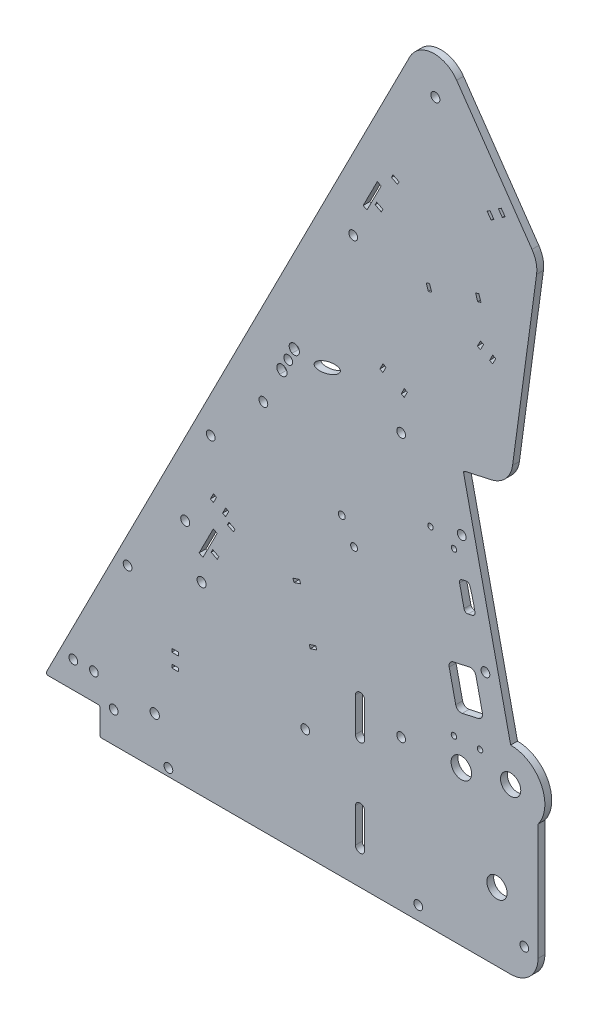
SolidWorks part; units mm, degrees
other "Markup1"
sketch "Sketch5"
ref_plane "Front Plane" through (0, 0, 0) normal (0, 0, 1) x (1, 0, 0)
ref_plane "Top Plane" through (0, 0, 0) normal (0, 1, 0) x (1, 0, 0)
ref_plane "Right Plane" through (0, 0, 0) normal (1, 0, 0) x (0, 0, -1)
sketch "Sketch1" plane through (0, 0, 0) normal (0, 0, 1) x (1, 0, 0)
  line L1 (228.6, -12.7) -> (228.6, 53.975)
  line L2 (178.7547, 351.4131) -> (0, 0)
  line L3 (228.6, 279.4) -> (178.7547, 351.4131)
  line L5 (0, 0) -> (25.4, 0)
  line L6 (25.4, 0) -> (25.4, -12.7)
  line L7 (25.4, -12.7) -> (228.6, -12.7)
  line L9 (215.9, 79.375) -> (193.9097, 178.5667)
  line L10 (193.9097, 178.5667) -> (215.6079, 183.377)
  line L11 (215.6079, 183.377) -> (228.6, 279.4)
  arc A0 (228.6, 53.975) -> (215.9, 79.375) centre (215.9, 63.5) ccw
  dimension "D7" = 12.7
  dimension "D8" = 76.2
  dimension "D10" = 31.75
  dimension "D2" = 292.1
  dimension "D3" = 25.4
  dimension "D4" = 215.9
  dimension "D5" = 394.2644
  dimension "D6" = 203.2
  dimension "D9" = 63.039
  dimension "D11" = 101.6
  dimension "D12" = 12.5
  dimension "D13" = 22.225
extrude "Boss-Extrude1" add sketch "Sketch1" along normal blind 3.175
sketch "Sketch2" plane through (0, 0, 3.175) normal (0, 0, 1) x (1, 0, 0)
  line L0 (178.7547, 351.4131) -> (0, 0) construction
  line L1 (25.4, -12.7) -> (228.6, -12.7) construction
  line L2 (215.9, 79.375) -> (193.9097, 178.5667) construction
  line L3 (193.9097, 178.5667) -> (215.6079, 183.377) construction
  line L4 (215.9, 79.375) -> (193.9097, 178.5667) construction
  line L5 (64.9432, 94.0578) -> (72.5445, 73.1732) construction
  line L6 (64.9432, 94.0578) -> (89.8317, 94.0578) construction
  line L10 (228.6, -12.7) -> (228.6, 53.975) construction
  circle A0 centre (64.9432, 94.0578) radius 2.0955
  circle A1 centre (180.975, 322.1643) radius 2.0955
  circle A2 centre (72.5445, 73.1732) radius 2.0955
  circle A3 centre (193.2078, 152.3944) radius 2.032
  circle A4 centre (215.9, 63.5) radius 4.699
  circle A7 centre (173.0375, -6.35) radius 2.032
  circle A8 centre (204.203, 102.7985) radius 2.032
  circle A26 centre (209.55, 19.05) radius 4.699
  arc A30 (228.6, 53.975) -> (215.9, 79.375) centre (215.9, 63.5) ccw construction
  circle A31 centre (165.1, 179.3875) radius 2.032
  point P5 (77.3874, 112.6024)
  point P17 (78.6277, 76.5455)
  dimension "D3" = 4.191
  dimension "D5" = 4.191
  dimension "D9" = 4.191
  dimension "D20" = 9.398
  dimension "D23" = 9.398
  dimension "D18" = 4.064
  dimension "D26" = 4.064
  dimension "D14" = 4.064
  dimension "D2" = 15.24
  dimension "D6" = 15.24
  dimension "D7" = 22.225
  dimension "D21" = 44.45
  dimension "D22" = 6.35
  dimension "D19" = 160.3375
  dimension "D24" = 44.45
  dimension "D25" = 6.35
  dimension "D27" = 25.4
  dimension "D28" = 50.8
  dimension "D29" = 6.35
  dimension "D17" = 6.35
  dimension "D33" = 55.5625
  dimension "D15" = 114.3
  dimension "D4" = 180.975
  dimension "D8" = 70
extrude "Cut-Extrude1" cut sketch "Sketch2" against normal through all
sketch "Sketch7" plane through (0, 0, 3.175) normal (0, 0, 1) x (1, 0, 0)
  line L0 (146.05, 3.175) -> (146.05, 19.05) construction
  line L1 (143.891, 3.175) -> (143.891, 19.05)
  line L2 (148.209, 3.175) -> (148.209, 19.05)
  line L3 (146.05, 47.625) -> (146.05, 63.5) construction
  line L4 (143.891, 47.625) -> (143.891, 63.5)
  line L5 (148.209, 47.625) -> (148.209, 63.5)
  line L6 (25.4, -12.7) -> (228.6, -12.7) construction
  line L12 (228.6, -12.7) -> (228.6, 53.975) construction
  line L13 (25.4, -12.7) -> (228.6, -12.7) construction
  arc A0 (143.891, 3.175) -> (148.209, 3.175) centre (146.05, 3.175) ccw
  arc A1 (148.209, 19.05) -> (143.891, 19.05) centre (146.05, 19.05) ccw
  arc A2 (143.891, 47.625) -> (148.209, 47.625) centre (146.05, 47.625) ccw
  arc A3 (148.209, 63.5) -> (143.891, 63.5) centre (146.05, 63.5) ccw
  circle A8 centre (50.8, 9.525) radius 2.159
  point P2 (146.05, 11.1125)
  point P9 (146.05, 55.5625)
  dimension "D1" = 4.318
  dimension "D5" = 4.318
  dimension "D2" = 15.875
  dimension "D3" = 15.875
  dimension "D4" = 44.45
  dimension "D6" = 95.25
  dimension "D7" = 82.55
  dimension "D8" = 15.875
  dimension "D9" = 22.225
extrude "Cut-Extrude2" cut sketch "Sketch7" against normal through all
sketch "Sketch10" plane through (0, 0, 3.175) normal (0, 0, 1) x (1, 0, 0)
  circle A1 centre (165.1, 57.15) radius 2.032
  circle A2 centre (120.65, 38.1) radius 2.032
  circle A3 centre (13.0465, 12.3347) radius 2.032
  circle A4 centre (22.5715, 12.3347) radius 2.032
  circle A5 centre (38.2114, 62.6398) radius 2.032
  dimension "D1" = 4.064
  dimension "D2" = 4.064
  dimension "D4" = 63.5
  dimension "D5" = 69.85
extrude "Cut-Extrude3" cut sketch "Sketch10" against normal up to next
fillet "Fillet1" radius 12.7 4 edges at (228.6, -12.7, 1.5875) (178.7547, 351.4131, 1.5875) (215.6079, 183.377, 1.5875) (228.6, 279.4, 1.5875)
fillet "Fillet2" radius 0.7937 4 edges at (25.4, -12.7, 1.5875) (25.4, 0, 1.5875) (193.9097, 178.5667, 1.5875) (0, 0, 1.5875)
sketch "Sketch12" plane through (0, 0, 3.175) normal (0, 0, 1) x (1, 0, 0)
  circle A0 centre (31.75, 1.5875) radius 2.032
  circle A1 centre (222.25, 1.5875) radius 2.032
  circle A2 centre (57.15, -9.2075) radius 2.032
  circle A3 centre (57.15, -9.2075) radius 2.286 construction
  dimension "D1" = 4.064
  dimension "D2" = 4.064
extrude "Cut-Extrude5" cut sketch "Sketch12" against normal through all
sketch "Sketch13" plane through (0, 0, 3.175) normal (0, 0, 1) x (1, 0, 0)
  line L2 (194.6847, 178.7385) -> (206.9592, 181.4597) construction
  line L5 (199.2434, 101.699) -> (189.6226, 145.0954) construction
  line L6 (189.6022, 69.9806) -> (201.7089, 70.5092) construction
  line L7 (186.8444, 98.9502) -> (199.2434, 101.699)
  line L8 (186.8444, 98.9502) -> (190.9676, 80.3518)
  line L9 (190.9676, 80.3518) -> (203.3665, 83.1006)
  line L10 (199.2434, 101.699) -> (203.3665, 83.1006)
  line L11 (189.6022, 69.9806) -> (190.9676, 80.3518) construction
  line L12 (201.7089, 70.5092) -> (203.3665, 83.1006) construction
  line L13 (215.9, 79.375) -> (194.0815, 177.7917) construction
  line L14 (178.7216, 148.5324) -> (189.6226, 145.0954) construction
  line L15 (195.1281, 134.9336) -> (193.4153, 134.5539)
  line L16 (192.209, 132.6604) -> (194.2706, 123.3612)
  line L17 (196.1641, 122.1549) -> (198.1091, 122.5861)
  line L18 (211.4332, 99.5233) -> (205.2337, 98.1489) construction
  line L19 (198.3765, 158.4184) -> (211.4332, 99.5233) construction
  circle A0 centre (189.6022, 69.9806) radius 1.27
  circle A1 centre (201.7089, 70.5092) radius 1.27
  circle A2 centre (178.7216, 148.5324) radius 1.27
  circle A3 centre (189.6226, 145.0954) radius 1.27
  arc A4 (199.3306, 124.402) -> (196.9796, 133.88) centre (134.9024, 113.4517) ccw
  arc A6 (199.4957, 103.5221) -> (189.2475, 149.7492) centre (134.9024, 113.4517) ccw construction
  arc A7 (195.1281, 134.9336) -> (196.9796, 133.88) centre (195.4717, 133.3837) cw
  arc A8 (198.1091, 122.5861) -> (199.3306, 124.402) centre (197.7655, 124.136) ccw
  arc A9 (194.2706, 123.3612) -> (196.1641, 122.1549) centre (195.8205, 123.7048) ccw
  arc A10 (193.4153, 134.5539) -> (192.209, 132.6604) centre (193.7589, 133.004) ccw
  point P26 (208.3335, 98.8361)
  point P31 (196.515, 135.2411)
  point P36 (194.6142, 121.8113)
  point P39 (191.8654, 134.2103)
  dimension "D7" = 2.54
  dimension "D16" = 1.5875
  dimension "D2" = 11.43
  dimension "D3" = 76.2
  dimension "D4" = 12.7
  dimension "D5" = 19.05
  dimension "D6" = 120
  dimension "D8" = 110
  dimension "D9" = 80
  dimension "D10" = 12.7
  dimension "D11" = 44.45
  dimension "D12" = 11.43
  dimension "D13" = 12.7
  dimension "D14" = 4.7625
  dimension "D15" = 38.1
extrude "Cut-Extrude6" cut sketch "Sketch13" against normal through all both and the other way through all
sketch "Sketch14" plane through (0, 0, 3.175) normal (0, 0, 1) x (1, 0, 0)
  line L0 (26.1937, -12.7) -> (215.9, -12.7) construction
  line L1 (228.6, 0) -> (228.6, 53.975) construction
  line L2 (112.7125, 182.5625) -> (101.1964, 159.9231) construction
  line L3 (169.1053, 332.4434) -> (0.5868, 1.1536) construction
  line L4 (112.7125, 182.5625) -> (136.864, 190.4279) construction
  line L5 (147.4827, 261.9243) -> (154.0469, 274.8287)
  line L6 (147.4827, 261.9243) -> (149.2654, 261.0175)
  line L7 (154.0469, 274.8287) -> (155.8295, 273.922)
  line L8 (149.2654, 261.0175) -> (155.8295, 273.922)
  line L9 (169.1053, 332.4434) -> (0.5868, 1.1536) construction
  line L10 (160.5905, 279.7801) -> (161.3102, 281.1951)
  line L11 (160.5905, 279.7801) -> (163.4204, 278.3406)
  line L12 (161.3102, 281.1951) -> (164.1402, 279.7556)
  line L13 (163.4204, 278.3406) -> (164.1402, 279.7556)
  line L14 (153.7897, 266.4104) -> (156.6196, 264.9709)
  line L15 (153.7897, 266.4104) -> (153.0699, 264.9954)
  line L16 (156.6196, 264.9709) -> (155.8998, 263.5559)
  line L17 (153.0699, 264.9954) -> (155.8998, 263.5559)
  line L19 (178.2697, 245.9923) -> (179.2404, 242.9693)
  line L20 (178.2697, 245.9923) -> (176.7582, 245.5069)
  line L21 (179.2404, 242.9693) -> (177.7289, 242.4839)
  line L22 (176.7582, 245.5069) -> (177.7289, 242.4839)
  line L24 (200.6096, 249.8308) -> (199.639, 252.8538)
  line L25 (200.6096, 249.8308) -> (202.1211, 250.3161)
  line L26 (199.639, 252.8538) -> (201.1505, 253.3391)
  line L27 (202.1211, 250.3161) -> (201.1505, 253.3391)
  line L34 (77.9534, 97.2255) -> (79.736, 96.3187)
  line L47 (77.9534, 97.2255) -> (71.3892, 84.3211)
  line L56 (79.736, 96.3187) -> (73.1718, 83.4143)
  line L57 (71.3892, 84.3211) -> (73.1718, 83.4143)
  line L58 (85.2167, 103.5918) -> (84.497, 102.1769)
  line L59 (85.2167, 103.5918) -> (88.0466, 102.1523)
  line L60 (84.497, 102.1769) -> (87.3269, 100.7374)
  line L61 (88.0466, 102.1523) -> (87.3269, 100.7374)
  line L62 (156.643, 199.3999) -> (158.0826, 202.2298)
  line L63 (156.643, 199.3999) -> (155.2281, 200.1197)
  line L64 (158.0826, 202.2298) -> (156.6676, 202.9496)
  line L65 (155.2281, 200.1197) -> (156.6676, 202.9496)
  line L66 (165.1328, 195.0814) -> (166.5723, 197.9113)
  line L67 (165.1328, 195.0814) -> (166.5478, 194.3617)
  line L68 (166.5723, 197.9113) -> (167.9873, 197.1916)
  line L69 (166.5478, 194.3617) -> (167.9873, 197.1916)
  line L78 (77.6961, 88.8072) -> (76.9764, 87.3922)
  line L79 (201.9154, 234.7497) -> (200.4759, 231.9198)
  line L80 (201.9154, 234.7497) -> (203.3303, 234.0299)
  line L81 (200.4759, 231.9198) -> (201.8908, 231.2)
  line L82 (203.3303, 234.0299) -> (201.8908, 231.2)
  line L83 (206.1357, 229.0407) -> (207.5752, 231.8707)
  line L84 (206.1357, 229.0407) -> (207.5507, 228.321)
  line L85 (207.5752, 231.8707) -> (208.9902, 231.1509)
  line L86 (207.5507, 228.321) -> (208.9902, 231.1509)
  line L88 (205.014, 288.3715) -> (206.821, 285.7609)
  line L89 (205.014, 288.3715) -> (206.3193, 289.275)
  line L90 (206.821, 285.7609) -> (208.1263, 286.6644)
  line L91 (206.3193, 289.275) -> (208.1263, 286.6644)
  line L92 (210.2352, 291.9855) -> (212.0422, 289.3749)
  line L93 (210.2352, 291.9855) -> (211.5405, 292.889)
  line L94 (212.0422, 289.3749) -> (213.3475, 290.2784)
  line L95 (211.5405, 292.889) -> (213.3475, 290.2784)
  line L96 (225.7968, 283.4499) -> (190.8675, 333.9133) construction
  line L97 (77.6961, 88.8072) -> (80.5261, 87.3677)
  line L98 (76.9764, 87.3922) -> (79.8063, 85.9527)
  line L99 (80.5261, 87.3677) -> (79.8063, 85.9527)
  line L100 (122.4534, 73.1037) -> (122.9512, 71.5963)
  line L101 (122.4534, 73.1037) -> (125.4682, 74.0993)
  line L102 (122.9512, 71.5963) -> (125.9661, 72.5919)
  line L103 (125.4682, 74.0993) -> (125.9661, 72.5919)
  line L104 (114.9173, 95.9228) -> (115.4151, 94.4154)
  line L105 (114.9173, 95.9228) -> (117.9322, 96.9185)
  line L106 (115.4151, 94.4154) -> (118.43, 95.411)
  line L107 (117.9322, 96.9185) -> (118.43, 95.411)
  line L108 (73.3338, 88.1438) -> (77.899, 97.1186) construction
  line L109 (75.1164, 87.2371) -> (79.6816, 96.2118) construction
  line L110 (76.2812, 89.5269) -> (86.5313, 84.313) construction
  line L111 (83.082, 102.8966) -> (93.3321, 97.6827) construction
  line L112 (121.934, 72.0825) -> (123.4755, 75.113) construction
  line L113 (127.9171, 72.8537) -> (123.4755, 75.113) construction
  line L114 (112.3753, 83.5081) -> (119.5388, 97.5909) construction
  line L115 (112.1491, 96.0767) -> (117.4079, 93.4017) construction
  line L116 (149.0052, 264.9173) -> (147.5544, 262.0651) construction
  line L117 (150.7878, 264.0106) -> (151.2099, 264.8403) construction
  line L118 (162.6248, 261.9162) -> (152.3747, 267.1302) construction
  line L119 (169.4256, 275.2859) -> (159.1755, 280.4999) construction
  line L120 (199.3876, 252.3597) -> (200.1584, 253.8749) construction
  line L121 (198.6169, 250.8445) -> (203.0585, 248.5852) construction
  line L122 (203.2698, 247.9167) -> (195.3067, 232.262) construction
  line L123 (180.2625, 244.9786) -> (175.0037, 247.6536) construction
  line L124 (178.1316, 240.7894) -> (185.2951, 254.8722) construction
  line L125 (190.7763, 226.1672) -> (185.5176, 228.8422) construction
  line L126 (58.7375, 39.6875) -> (61.9125, 39.6875)
  line L127 (58.7375, 39.6875) -> (58.7375, 38.1)
  line L128 (61.9125, 39.6875) -> (61.9125, 38.1)
  line L129 (58.7375, 38.1) -> (61.9125, 38.1)
  line L130 (58.7375, 33.3375) -> (61.9125, 33.3375)
  line L131 (58.7375, 33.3375) -> (58.7375, 31.75)
  line L132 (61.9125, 33.3375) -> (61.9125, 31.75)
  line L133 (58.7375, 31.75) -> (61.9125, 31.75)
  line L135 (78.0516, 111.4242) -> (76.6121, 108.5943)
  line L136 (78.0516, 111.4242) -> (79.4665, 110.7045)
  line L137 (76.6121, 108.5943) -> (78.027, 107.8745)
  line L138 (79.4665, 110.7045) -> (78.027, 107.8745)
  line L139 (82.2719, 105.7153) -> (83.7114, 108.5452)
  line L140 (82.2719, 105.7153) -> (83.6869, 104.9955)
  line L141 (83.7114, 108.5452) -> (85.1264, 107.8254)
  line L142 (83.6869, 104.9955) -> (85.1264, 107.8254)
  circle A0 centre (142.875, 247.65) radius 2.032
  circle A1 centre (112.7125, 182.5625) radius 2.032
  circle A2 centre (101.1964, 159.9231) radius 2.032
  circle A3 centre (-3.6715, -75.3714) radius 1.6 construction
  circle A4 centre (-8.8402, -85.5324) radius 1.6 construction
  circle A5 centre (137.5592, 132.521) radius 1.6 construction
  circle A6 centre (143.2592, 122.6483) radius 1.6 construction
  circle A7 centre (-3.6715, -75.3714) radius 1.6
  circle A8 centre (-8.8402, -85.5324) radius 1.6
  circle A9 centre (137.5592, 132.521) radius 1.6
  circle A10 centre (143.2592, 122.6483) radius 1.6
  arc A13 (0, 1.5875) -> (1.5875, 0) centre (1.5875, 1.5875) ccw construction
  ellipse E0 centre (109.8335, 176.9027) end of major axis (108.7539, 174.7802) minor radius 2.32 (108.7539, 174.7802) -> (110.9131, 179.0251) ccw construction
  ellipse E1 centre (109.8335, 176.9027) end of major axis (108.7539, 174.7802) minor radius 2.32 (108.7539, 174.7802) -> (110.9131, 179.0251) ccw
  ellipse E2 centre (130.8261, 188.4615) end of major axis (124.7883, 186.4952) minor radius 2.3812
  ellipse E3 centre (115.5915, 188.2223) end of major axis (116.6711, 190.3448) minor radius 2.32 (114.5119, 186.0999) -> (116.6711, 190.3448) ccw construction
  ellipse E4 centre (115.5915, 188.2223) end of major axis (114.5119, 186.0999) minor radius 2.32 (114.5119, 186.0999) -> (116.6711, 190.3448) ccw
  spline S0 degree 3 poles (603.8918, 1049.0657) (-166.9189, -675.3083) (147.8077, 168.3802) (110.3225, 179.2425) (110.1654, 179.2721) (109.6955, 179.3152) (109.3734, 179.2831) (108.9218, 179.1456) (108.7737, 179.0841) (108.4954, 178.9343) (108.365, 178.8464) (108.1219, 178.6442) (108.0097, 178.5297) (107.8134, 178.2839) (107.7278, 178.1512) (107.5834, 177.8672) (107.527, 177.7202) (107.4441, 177.4168) (107.4178, 177.2585) (107.3978, 176.9432) (107.4036, 176.7863) (107.4465, 176.4736) (107.4841, 176.3175) (107.5874, 176.0205) (107.6532, 175.8777) (107.8133, 175.6037) (107.9066, 175.4748) (114.8282, 167.6036) (173.9427, 200.577) (-567.4982, 911.3293) knots -15.287416 -15.287416 -15.287416 -15.287416 0.0625 0.0625 0.125 0.125 0.25 0.25 0.3125 0.3125 0.375 0.375 0.4375 0.4375 0.5 0.5 0.5625 0.5625 0.625 0.625 0.6875 0.6875 0.75 0.75 0.8125 0.8125 0.875 0.875 4.983329 4.983329 4.983329 4.983329 only from (110.9131, 179.0251) to (108.7539, 174.7802) construction
  spline S1 degree 3 poles (110.9131, 179.0251) (110.7727, 179.0965) (110.6265, 179.1544) (110.3225, 179.2425) (110.1654, 179.2721) (109.6955, 179.3152) (109.3734, 179.2831) (108.9218, 179.1456) (108.7737, 179.0841) (108.4954, 178.9343) (108.365, 178.8464) (108.1219, 178.6442) (108.0097, 178.5297) (107.8134, 178.2839) (107.7278, 178.1512) (107.5834, 177.8672) (107.527, 177.7202) (107.4441, 177.4168) (107.4178, 177.2585) (107.3978, 176.9432) (107.4036, 176.7863) (107.4465, 176.4736) (107.4841, 176.3175) (107.5874, 176.0205) (107.6532, 175.8777) (107.8133, 175.6037) (107.9066, 175.4748) (108.2178, 175.121) (108.4736, 174.9228) (108.7539, 174.7802) knots 0 0 0 0 0.0625 0.0625 0.125 0.125 0.25 0.25 0.3125 0.3125 0.375 0.375 0.4375 0.4375 0.5 0.5 0.5625 0.5625 0.625 0.625 0.6875 0.6875 0.75 0.75 0.8125 0.8125 0.875 0.875 1 1 1 1
  spline S2 degree 3 poles (-635.3332, 847.705) (160.0375, 206.8561) (120.8424, 181.1302) (113.9875, 186.4501) (113.8729, 186.5577) (113.5583, 186.9155) (113.3974, 187.1901) (113.2413, 187.6401) (113.2046, 187.793) (113.1618, 188.1044) (113.1558, 188.2648) (113.176, 188.5797) (113.2018, 188.7347) (113.2848, 189.0394) (113.3426, 189.1891) (113.5563, 189.6095) (113.7586, 189.8627) (114.1212, 190.1647) (114.2542, 190.2544) (114.5324, 190.4041) (114.6775, 190.4645) (114.9798, 190.5567) (115.1369, 190.5882) (115.4499, 190.6199) (115.6074, 190.6207) (115.9244, 190.5918) (116.0795, 190.5623) (125.0451, 187.9725) (125.4505, 134.6135) (-868.6048, 361.2821) knots -3.325634 -3.325634 -3.325634 -3.325634 0.0625 0.0625 0.125 0.125 0.25 0.25 0.3125 0.3125 0.375 0.375 0.4375 0.4375 0.5 0.5 0.625 0.625 0.6875 0.6875 0.75 0.75 0.8125 0.8125 0.875 0.875 0.9375 0.9375 4.586013 4.586013 4.586013 4.586013 only from (114.5119, 186.0999) to (116.6711, 190.3448) construction
  spline S3 degree 3 poles (114.5119, 186.0999) (114.3711, 186.1715) (114.2359, 186.2574) (113.9875, 186.4501) (113.8729, 186.5577) (113.5583, 186.9155) (113.3974, 187.1901) (113.2413, 187.6401) (113.2046, 187.793) (113.1618, 188.1044) (113.1558, 188.2648) (113.176, 188.5797) (113.2018, 188.7347) (113.2848, 189.0394) (113.3426, 189.1891) (113.5563, 189.6095) (113.7586, 189.8627) (114.1212, 190.1647) (114.2542, 190.2544) (114.5324, 190.4041) (114.6775, 190.4645) (114.9798, 190.5567) (115.1369, 190.5882) (115.4499, 190.6199) (115.6074, 190.6207) (115.9244, 190.5918) (116.0795, 190.5623) (116.3815, 190.4751) (116.53, 190.4166) (116.6711, 190.3448) knots 0 0 0 0 0.0625 0.0625 0.125 0.125 0.25 0.25 0.3125 0.3125 0.375 0.375 0.4375 0.4375 0.5 0.5 0.625 0.625 0.6875 0.6875 0.75 0.75 0.8125 0.8125 0.875 0.875 0.9375 0.9375 1 1 1 1
  point P179 (82.9794, 105.3554)
  dimension "D1" = 4.064
  dimension "D15" = 3.175
  dimension "D2" = 195.2625
  dimension "D3" = 115.8875
  dimension "D4" = 85.725
  dimension "D5" = 260.35
  dimension "D6" = 25.4
  dimension "D7" = 4.7625
  dimension "D8" = 12.7
  dimension "D9" = 19.05
  dimension "D10" = 45
  dimension "D11" = 6.858
  dimension "D12" = 7.62
  dimension "D13" = 3.175
  dimension "D14" = 1.5875
  dimension "D16" = 1.5875
  dimension "D17" = 1.5875
  dimension "D18" = 9.525
  dimension "D19" = 47.625
  dimension "D20" = 38.1
  dimension "D21" = 6.858
  dimension "D22" = 7.62
  dimension "D23" = 1.5875
  dimension "D24" = 3.175
  dimension "D25" = 1.5875
  dimension "D26" = 4.7625
  dimension "D27" = 4.7625
  dimension "D28" = 1.5875
  dimension "D29" = 3.175
  dimension "D30" = 9.525
  dimension "D31" = 4.7625
  dimension "D32" = 4.7625
  dimension "D33" = 1.5875
  dimension "D34" = 3.175
  dimension "D35" = 6.35
  dimension "D36" = 12.7
  dimension "D37" = 1.5875
  dimension "D38" = 3.175
  dimension "D39" = 9.525
  dimension "D40" = 57.15
  dimension "D41" = 44.45
  dimension "D42" = 1.5875
  dimension "D43" = 4.7625
  dimension "D44" = 3.175
extrude "Cut-Extrude7" cut sketch "Sketch14" against normal through all
sketch "Sketch15" plane through (0, 0, 3.175) normal (0, 0, 1) x (1, 0, 0)
  line L0 (169.1053, 332.4434) -> (0.5868, 1.1536) construction
  circle A0 centre (76.7868, 134.1481) radius 2.032
  circle A1 centre (-0.801, -29.586) radius 2.032
  circle A2 centre (-6.559, -40.9057) radius 2.032
  circle A3 centre (-0.801, -29.586) radius 1.905 construction
  circle A4 centre (-6.559, -40.9057) radius 1.905 construction
  dimension "D1" = 4.064
  dimension "D4" = 4.064
  dimension "D2" = 7.62
  dimension "D3" = 76.2
extrude "Cut-Extrude8" cut sketch "Sketch15" against normal through all
fillet "Fillet3" radius 2.54 4 edges at (199.2434, 101.699, 1.5875) (186.8444, 98.9502, 1.5875) (190.9676, 80.3518, 1.5875) (203.3665, 83.1006, 1.5875)
sketch "Sketch16" plane through (0, 0, 3.175) normal (0, 0, 1) x (1, 0, 0)
  line L0 (228.6, 0) -> (228.6, 53.975) construction
  line L1 (26.1937, -12.7) -> (215.9, -12.7) construction
  circle A0 centre (193.04, 58.801) radius 4.7625
  dimension "D1" = 9.525
  dimension "D2" = 35.56
  dimension "D3" = 71.501
extrude "Cut-Extrude9" cut sketch "Sketch16" against normal through all
equation "\"D6@Sketch2\"=\"D2@Sketch2\""
